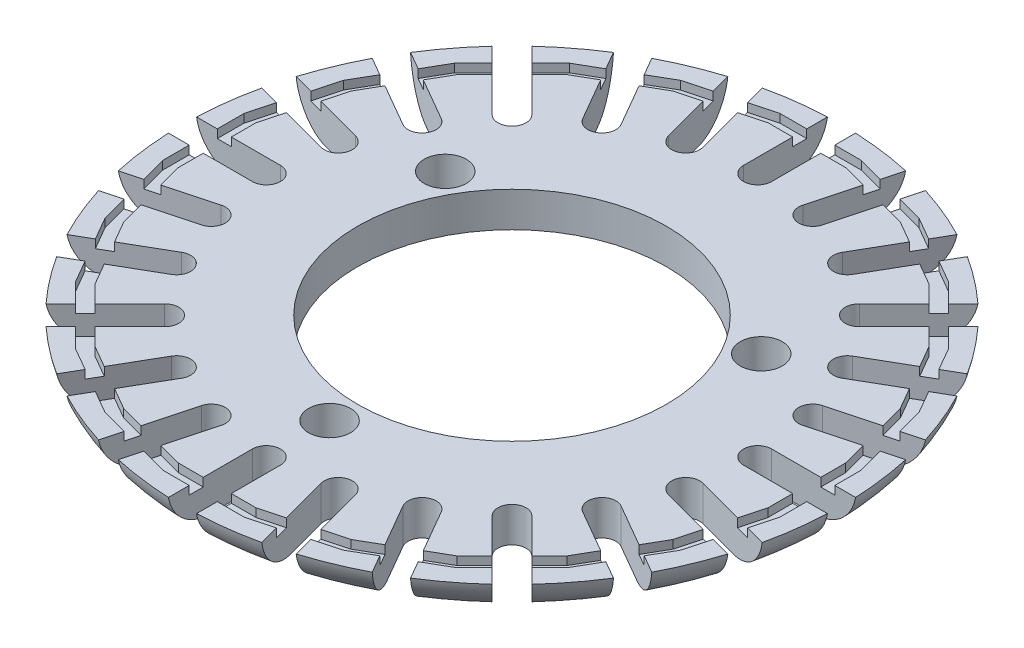
SolidWorks part; units mm, degrees
ref_plane "Plano frontal" through (0, 0, 0) normal (0, 0, 1) x (1, 0, 0)
ref_plane "Plano superior" through (0, 0, 0) normal (0, 1, 0) x (1, 0, 0)
ref_plane "Plano direito" through (0, 0, 0) normal (1, 0, 0) x (0, 0, -1)
sketch "Esboço1" plane through (0, 0, 0) normal (0, 1, 0) x (1, 0, 0)
  circle A0 centre (0, 0) radius 23.5
  dimension "D1" = 47
extrude "Ressalto-extrusão1" add sketch "Esboço1" along normal blind 2.5
fillet "Filete1" radius 3 1 edges at (0, 0, 23.5)
sketch "Esboço2" plane through (0, 2.5, 0) normal (0, 1, 0) x (1, 0, 0)
  line L0 (0, 0) -> (0, 23.9078) construction
  line L2 (1, 17.5) -> (1, 23.5)
  line L3 (1, 23.5) -> (-1, 23.5)
  line L4 (0, 23.5) -> (7.8408, 23.5) construction
  line L5 (-1, 17.5) -> (-1, 23.5)
  arc A0 (-1, 17.5) -> (1, 17.5) centre (0, 17.5) ccw
  circle A3 centre (0, 0) radius 23.5 construction
  point P12 (0, 16.5)
  dimension "D2" = 6
  dimension "D1" = 1
extrude "Corte-extrusão1" cut sketch "Esboço2" against normal through all
pattern_circular "PadrãoCircular1" count 24 over 360 about axis through (0, 2.5, 0) along (0, 1, 0) of "Corte-extrusão1"
sketch "Esboço4" plane through (0, 2.5, 0) normal (0, 1, 0) x (1, 0, 0)
  line L0 (0, 0) -> (-3.0674, 23.299) construction
  line L1 (0, 0) -> (3.0674, 23.299) construction
  line L2 (-2.8964, 22) -> (2.8964, 22)
  line L3 (2.8964, 22) -> (2.7647, 21)
  line L4 (2.7647, 21) -> (-2.7647, 21)
  line L5 (-2.7647, 21) -> (-2.8964, 22)
  arc A2 (5.1108, 22.9375) -> (1, 23.4787) centre (0, 0) ccw construction
  arc A3 (-1, 23.4787) -> (-5.1108, 22.9375) centre (0, 0) ccw construction
  dimension "D1" = 1
  dimension "D2" = 21
extrude "Corte-extrusão2" cut sketch "Esboço4" against normal blind 0.6
pattern_circular "PadrãoCircular2" count 24 over 360 about axis through (0, 2.5, 0) along (0, 1, 0) of "Corte-extrusão2"
sketch "Esboço5" plane through (0, 2.5, 0) normal (0, 1, 0) x (1, 0, 0)
  circle A0 centre (0, 0) radius 11
  dimension "D1" = 22
extrude "Corte-extrusão3" cut sketch "Esboço5" against normal through all
sketch "Esboço6" plane through (0, 2.5, 0) normal (0, 1, 0) x (1, 0, 0)
  circle A4 centre (-11.2583, 6.5) radius 1.5
  circle A5 centre (11.2583, 6.5) radius 1.5
  circle A6 centre (0, -13) radius 1.5
  dimension "D5" = 3
extrude "Corte-extrusão5" cut sketch "Esboço6" against normal blind 2.5
